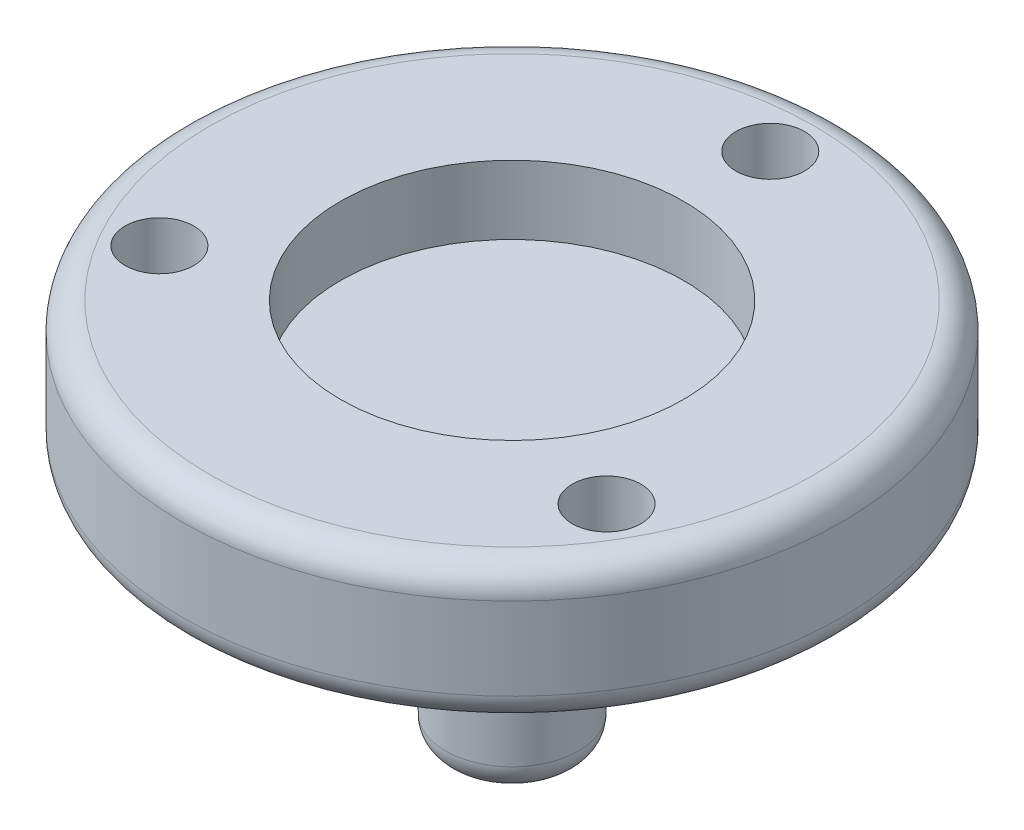
SolidWorks part; units mm, degrees
ref_plane "Front Plane" through (0, 0, 0) normal (0, 0, 1) x (1, 0, 0)
ref_plane "Top Plane" through (0, 0, 0) normal (0, 1, 0) x (1, 0, 0)
ref_plane "Right Plane" through (0, 0, 0) normal (1, 0, 0) x (0, 0, -1)
sketch "Sketch1" plane through (0, 0, 0) normal (0, 1, 0) x (1, 0, 0)
  circle A0 centre (0, 0) radius 15.24
extrude "Boss-Extrude1" add sketch "Sketch1" along normal blind 6.35
sketch "Sketch2" plane through (0, 6.35, 0) normal (0, 1, 0) x (1, 0, 0)
  circle A0 centre (0, 0) radius 7.9375
extrude "Cut-Extrude1" cut sketch "Sketch2" against normal blind 3.175
sketch "Sketch3" plane through (0, 0, 0) normal (0, -1, 0) x (1, 0, 0)
  circle A0 centre (0, 0) radius 3.0734
fillet "Fillet4" radius 1.27 1 edges at (0, 6.35, 15.24)
sketch "Sketch4" plane through (0, 6.35, 0) normal (0, 1, 0) x (1, 0, 0)
  line L0 (0, 0) -> (0, 13.97) construction
  circle A0 centre (0, 0) radius 13.97 construction
  circle A1 centre (0, 0) radius 11.938 construction
  circle A2 centre (0, 11.938) radius 1.5875
extrude "Cut-Extrude2" cut sketch "Sketch4" against normal blind 2.54
ref_axis "Axis1" through (0, 3.175, 0) along (0, 1, 0)
pattern_circular "CirPattern1" count 3 every 120 about axis through (0, 3.175, 0) along (0, 1, 0) of "Cut-Extrude2" reverse direction yes
fillet "Fillet6" radius 1.27 1 edges at (0, 0, 15.24)
extrude "Boss-Extrude4" add sketch "Sketch3" along normal blind 11.43 contours A0
fillet "Fillet7" radius 1.27 2 edges at (0, -11.43, -3.0734) (0, 0, 3.0734)
